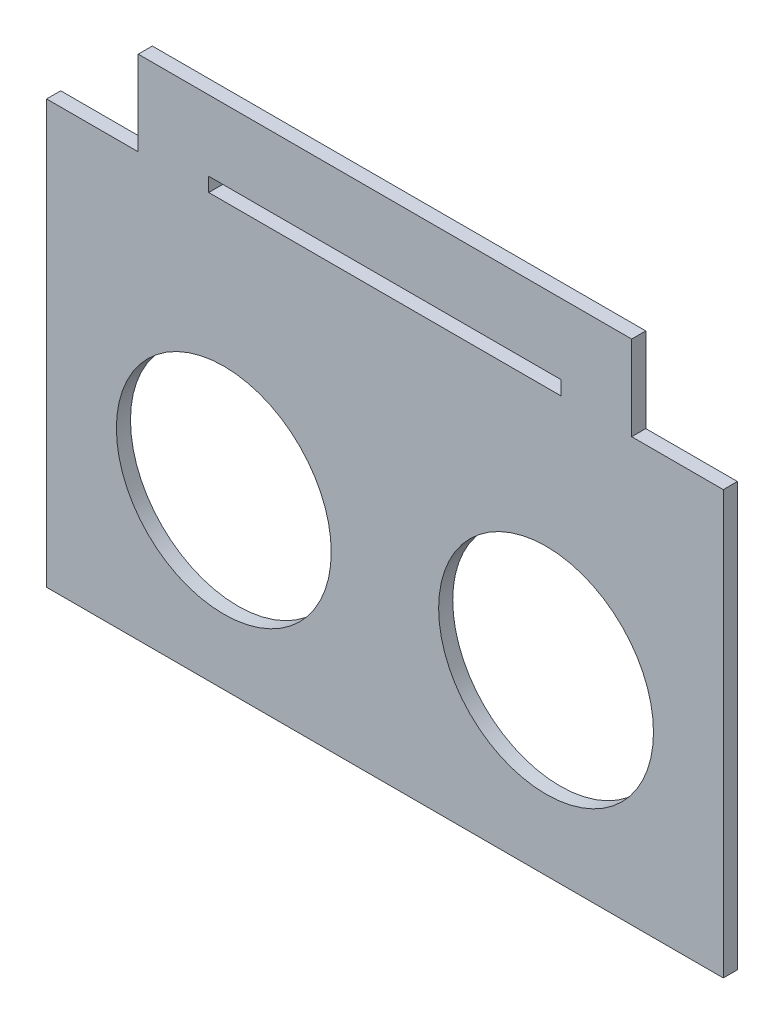
SolidWorks part; units mm, degrees
ref_plane "Přední rovina" through (0, 0, 0) normal (0, 0, 1) x (1, 0, 0)
ref_plane "Horní rovina" through (0, 0, 0) normal (0, 1, 0) x (1, 0, 0)
ref_plane "Pravá rovina" through (0, 0, 0) normal (1, 0, 0) x (0, 0, -1)
sketch "Skica1" plane through (0, 0, 0) normal (0, 0, 1) x (1, 0, 0)
  line L1 (-19.7439, 5.4997) -> (28.2561, 5.4997)
  line L2 (-19.7439, 5.4997) -> (-19.7439, -24.5003)
  line L3 (-19.7439, -24.5003) -> (28.2561, -24.5003)
  line L4 (28.2561, 5.4997) -> (28.2561, -24.5003)
  line L5 (-13.2439, 5.4997) -> (21.7561, 5.4997)
  line L6 (-13.2439, 5.4997) -> (-13.2439, 11.4997)
  line L7 (-13.2439, 11.4997) -> (21.7561, 11.4997)
  line L8 (21.7561, 5.4997) -> (21.7561, 11.4997)
  line L9 (16.7561, 5.4997) -> (-8.2439, 5.4997)
  line L10 (16.7561, 5.4997) -> (16.7561, 6.4997)
  line L11 (16.7561, 6.4997) -> (-8.2439, 6.4997)
  line L12 (-8.2439, 5.4997) -> (-8.2439, 6.4997)
  circle A0 centre (-7.1739, -12.2502) radius 7.62
  circle A1 centre (15.6831, -11.8803) radius 7.62
  dimension "D1" = 22.86
  dimension "D2" = 15.24
  dimension "D3" = 15.24
  dimension "D9" = 12.57
  dimension "D13" = 17.38
  dimension "D4" = 5
  dimension "D5" = 5
  dimension "D6" = 5
  dimension "D7" = 1
  dimension "D8" = 25
  dimension "D10" = 48
  dimension "D11" = 6.5
  dimension "D12" = 30
extrude "Přidat vysunutím1" add sketch "Skica1" along normal blind 1 contours L4 L1 L5 L2 L3 A1 A0 | L1 L12 L11 L10 L8 L7 L6 region at (4.2566, -8.63, 0) region at (4.2561, 8.8375, 0)
